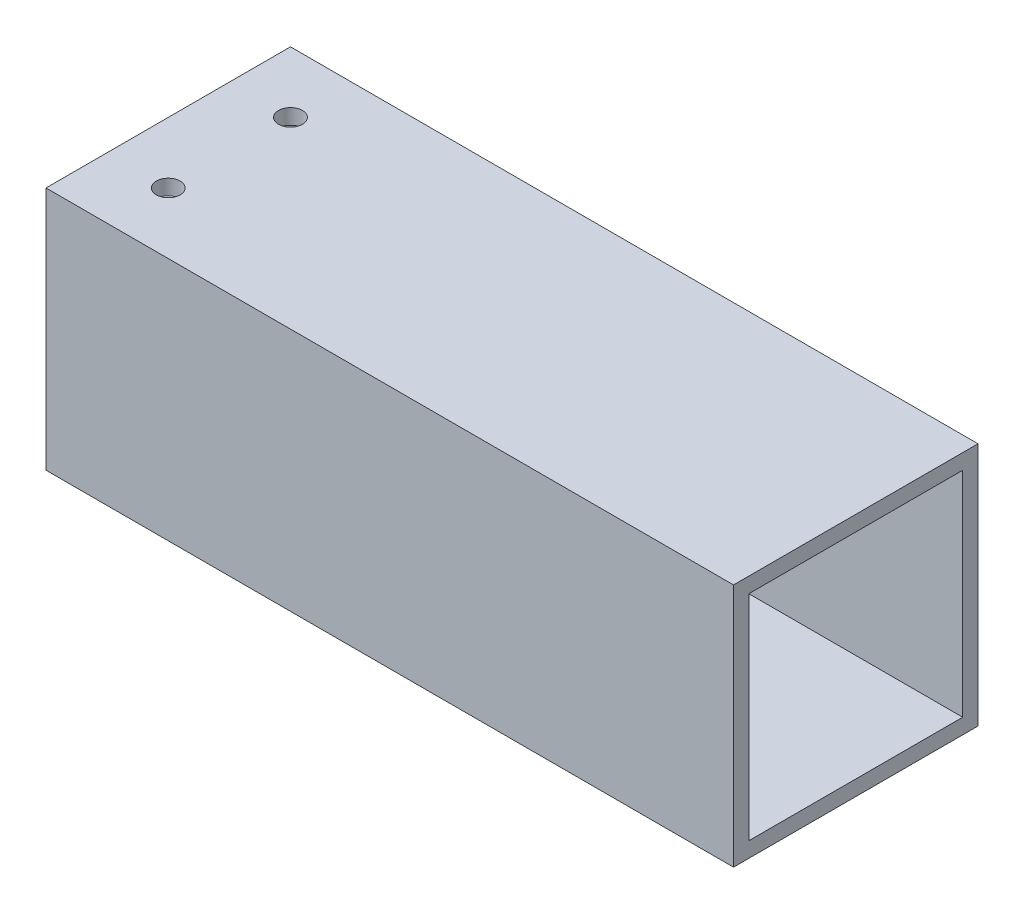
SolidWorks part; units mm, degrees
material "6061-T6 (SS)"
ref_plane "Front Plane" through (0, 0, 0) normal (0, 0, 1) x (1, 0, 0)
ref_plane "Top Plane" through (0, 0, 0) normal (0, 1, 0) x (1, 0, 0)
ref_plane "Right Plane" through (0, 0, 0) normal (1, 0, 0) x (0, 0, -1)
sketch "Sketch1" plane through (0, 0, 0) normal (1, 0, 0) x (0, 0, -1)
  line L1 (0, 0) -> (50.8, 0)
  line L2 (0, 0) -> (0, 50.8)
  line L3 (0, 50.8) -> (50.8, 50.8)
  line L4 (50.8, 0) -> (50.8, 50.8)
  dimension "D1" = 50.8
extrude "Boss-Extrude1" add sketch "Sketch1" along normal blind 142.875
shell "Shell1" thickness 3.175 removed face at (0, 25.4, -25.4) removed face at (142.875, 25.4, -25.4)
sketch "Sketch2" plane through (0, 0, -50.8) normal (0, 0, -1) x (-1, 0, 0)
  circle A0 centre (63.5, 38.1) radius 2.4892
  circle A1 centre (38.1, 38.1) radius 2.4892 construction
  circle A2 centre (63.5, 38.1) radius 2.4892 construction
  circle A3 centre (88.9, 38.1) radius 2.4892 construction
  circle A4 centre (63.5, 12.7) radius 2.4892
  circle A6 centre (88.9, 12.7) radius 2.4892 construction
  circle A7 centre (63.5, 12.7) radius 2.4892 construction
  circle A8 centre (38.1, 12.7) radius 2.4892 construction
  circle A10 centre (12.7, 38.1) radius 2.4892
  circle A11 centre (38.1, 38.1) radius 2.4892
  circle A12 centre (63.5, 38.1) radius 2.4892
  circle A13 centre (88.9, 38.1) radius 2.4892
  circle A14 centre (88.9, 38.1) radius 2.4892
  circle A15 centre (88.9, 12.7) radius 2.4892 construction
  circle A16 centre (88.9, 12.7) radius 2.4892
  circle A17 centre (63.5, 12.7) radius 2.4892
  circle A18 centre (38.1, 12.7) radius 2.4892
  circle A19 centre (12.7, 12.7) radius 2.4892
  point P1 (0, 0)
  dimension "D3" = 4.9784
  dimension "D1" = 25.4
  dimension "D2" = 25.4
  dimension "D7" = 2
extrude "Cut-Extrude1" cut sketch "Sketch2" against normal through all contours A16 | A13 | A4 | A0 | A18 | A11 | A19 | A10 rebuild error yes
sketch "Sketch3" plane through (0, 0, 0) normal (0, -1, 0) x (1, 0, 0)
  line L1 (12.7, -38.1) -> (12.7, -12.7) construction
  line L2 (12.7, -12.7) -> (12.7, 12.7) construction
  line L3 (171.45, 0) -> (-425.45, 0) construction
  line L4 (142.875, -50.8) -> (0, -50.8) construction
  circle A0 centre (12.7, -12.7) radius 2.4892
  circle A1 centre (12.7, -38.1) radius 2.4892
  dimension "D1" = 4.9784
  dimension "D2" = 12.7
  dimension "D3" = 12.7
extrude "Cut-Extrude2" cut sketch "Sketch3" against normal through all
pattern_linear "LPattern1" count 6 spacing 25.4 along (-1, 0, 0) of "Cut-Extrude2"
